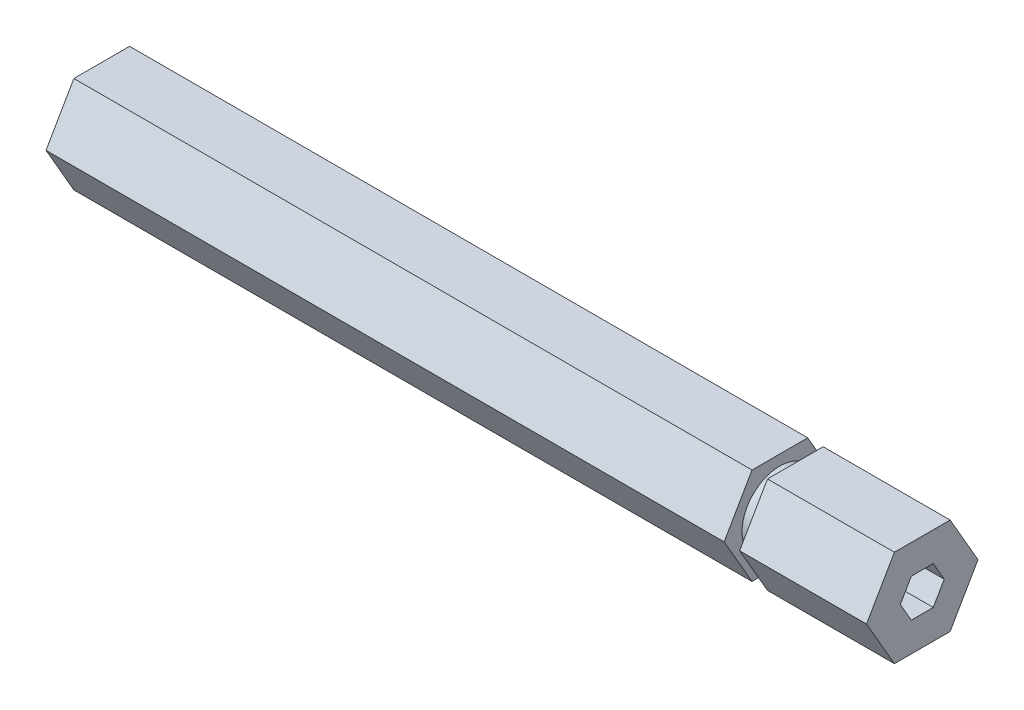
SolidWorks part; units mm, degrees
material "6061-T6 (SS)"
ref_plane "Front" through (0, 0, 0) normal (0, 0, 1) x (1, 0, 0)
ref_plane "Top" through (0, 0, 0) normal (0, 1, 0) x (1, 0, 0)
ref_plane "Right" through (0, 0, 0) normal (1, 0, 0) x (0, 0, -1)
sketch "Sketch1" plane through (0, 0, 0) normal (1, 0, 0) x (0, 0, -1)
  line L1 (7.3323, 0) -> (3.6662, 6.35)
  line L2 (3.6662, 6.35) -> (-3.6662, 6.35)
  line L3 (-3.6662, 6.35) -> (-7.3323, 0)
  line L4 (-7.3323, 0) -> (-3.6662, -6.35)
  line L5 (-3.6662, -6.35) -> (3.6662, -6.35)
  line L6 (3.6662, -6.35) -> (7.3323, 0)
  line L7 (2.8868, 0) -> (1.4434, 2.5)
  line L8 (1.4434, 2.5) -> (-1.4434, 2.5)
  line L9 (-1.4434, 2.5) -> (-2.8868, 0)
  line L10 (-2.8868, 0) -> (-1.4434, -2.5)
  line L11 (-1.4434, -2.5) -> (1.4434, -2.5)
  line L12 (1.4434, -2.5) -> (2.8868, 0)
  circle A0 centre (0, 0) radius 6.35 construction
  circle A1 centre (0, 0) radius 2.5 construction
  dimension "D1" = 12.7
  dimension "D2" = 5
extrude "Boss-Extrude1" add sketch "Sketch1" along normal blind 107.95
ref_axis "Axis1" through (-80.9, 0, 0) along (1, 0, 0)
sketch "Sketch2" plane through (0, 0, 0) normal (0, 1, 0) x (1, 0, 0)
  line L0 (107.95, 7.3323) -> (0, 7.3323) construction
  line L1 (89.2175, 7.3323) -> (91.2495, 7.3323)
  line L2 (89.2175, 7.3323) -> (89.2175, 4.9784)
  line L3 (89.2175, 4.9784) -> (91.2495, 4.9784)
  line L4 (91.2495, 7.3323) -> (91.2495, 4.9784)
  line L5 (0, 0) -> (21.2173, 0) construction
  line L7 (107.95, 3.6662) -> (107.95, -3.6662) construction
  dimension "D1" = 2.032
  dimension "D2" = 9.9568
  dimension "D3" = 16.7005
revolve "Cut-Revolve1" cut sketch "Sketch2" angle 360 about L5
